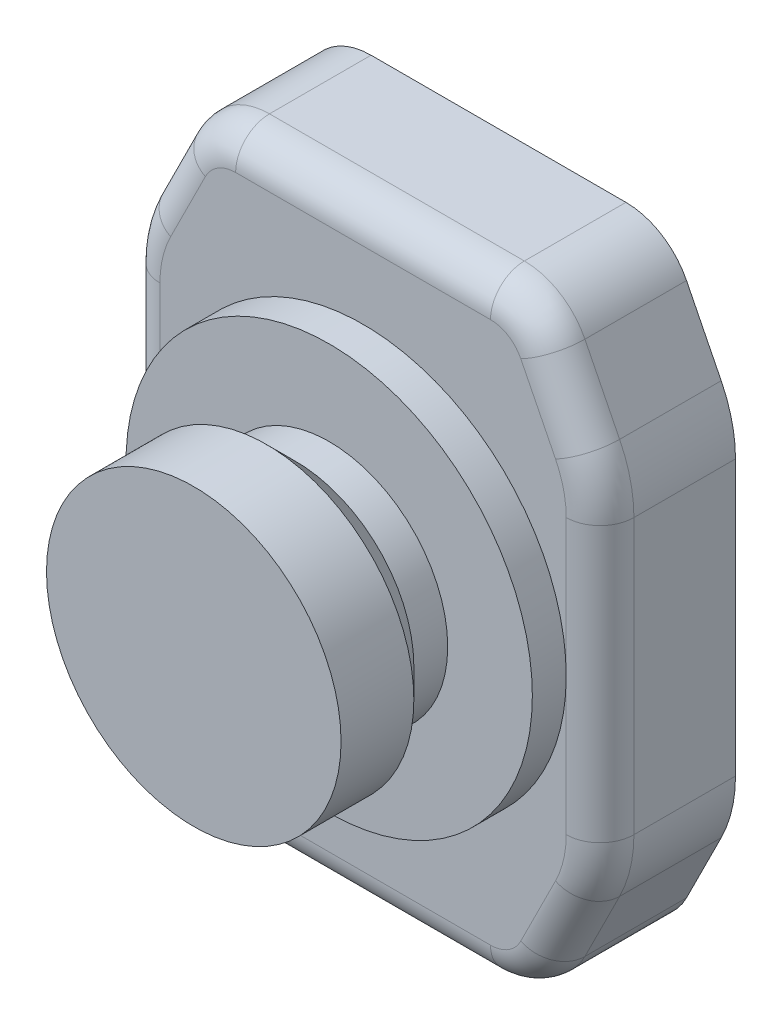
SolidWorks part; units mm, degrees
ref_plane "Front Plane" through (0, 0, 0) normal (0, 0, 1) x (1, 0, 0)
ref_plane "Top Plane" through (0, 0, 0) normal (0, 1, 0) x (1, 0, 0)
ref_plane "Right Plane" through (0, 0, 0) normal (1, 0, 0) x (0, 0, -1)
sketch "Sketch1" plane through (0, 0, 0) normal (0, 0, 1) x (1, 0, 0)
  line L0 (-32.8885, 29.2229) -> (-27.7639, 39.4721)
  line L1 (-18.8197, -45) -> (18.8197, -45)
  line L2 (-35, -20.2786) -> (-35, 20.2786)
  line L3 (-18.8197, 45) -> (18.8197, 45)
  line L4 (35, -20.2786) -> (35, 20.2786)
  line L5 (-35, -45) -> (35, 45) construction
  line L6 (-35, 45) -> (35, -45) construction
  line L7 (27.7639, 39.4721) -> (32.8885, 29.2229)
  line L8 (-32.8885, -29.2229) -> (-27.7639, -39.4721)
  line L9 (27.7639, -39.4721) -> (32.8885, -29.2229)
  arc A0 (-27.7639, -39.4721) -> (-18.8197, -45) centre (-18.8197, -35) ccw
  arc A1 (27.7639, -39.4721) -> (18.8197, -45) centre (18.8197, -35) cw
  arc A2 (27.7639, 39.4721) -> (18.8197, 45) centre (18.8197, 35) ccw
  arc A3 (-27.7639, 39.4721) -> (-18.8197, 45) centre (-18.8197, 35) cw
  arc A4 (32.8885, 29.2229) -> (35, 20.2786) centre (15, 20.2786) cw
  arc A5 (32.8885, -29.2229) -> (35, -20.2786) centre (15, -20.2786) ccw
  arc A6 (-32.8885, -29.2229) -> (-35, -20.2786) centre (-15, -20.2786) cw
  arc A7 (-32.8885, 29.2229) -> (-35, 20.2786) centre (-15, 20.2786) ccw
  point P0 (0, 0)
  point P16 (-25, -45)
  point P19 (25, -45)
  point P22 (25, 45)
  point P25 (-25, 45)
  point P28 (35, 25)
  point P31 (35, -25)
  point P34 (-35, -25)
  point P37 (-35, 25)
  dimension "D11" = 10
  dimension "D12" = 20
  dimension "D1" = 70
  dimension "D2" = 90
  dimension "D3" = 20
  dimension "D4" = 10
  dimension "D5" = 10
  dimension "D6" = 20
  dimension "D7" = 10
  dimension "D8" = 20
  dimension "D9" = 10
  dimension "D10" = 20
extrude "Boss-Extrude1" add sketch "Sketch1" along normal blind 20
fillet "Fillet1" radius 5 16 edges at (-30.3262, -34.3475, 20) (-34.465, -24.8737, 20) (-35, 0, 20) (-34.465, 24.8737, 20) (-30.3262, 34.3475, 20) (-24.077, 43.5065, 20) (0, 45, 20) (24.077, 43.5065, 20) (30.3262, 34.3475, 20) (34.465, 24.8737, 20) (35, 0, 20) (34.465, -24.8737, 20) (30.3262, -34.3475, 20) (24.077, -43.5065, 20) (0, -45, 20) (-24.077, -43.5065, 20)
sketch "Sketch2" plane through (0, 0, 20) normal (0, 0, 1) x (1, 0, 0)
  circle A0 centre (0, 0) radius 30
  dimension "D1" = 60
extrude "Boss-Extrude2" add sketch "Sketch2" along normal blind 5
sketch "Sketch3" plane through (0, 0, 25) normal (0, 0, 1) x (1, 0, 0)
  circle A0 centre (0, 0) radius 17.5
  dimension "D1" = 35
extrude "Boss-Extrude3" add sketch "Sketch3" along normal blind 10
sketch "Sketch4" plane through (0, 0, 35) normal (0, 0, 1) x (1, 0, 0)
  circle A0 centre (0, 0) radius 21.75
  dimension "D1" = 43.5
extrude "Boss-Extrude4" add sketch "Sketch4" along normal blind 10
chamfer "Chamfer1" distance 5 angle 45 1 edges at (17.5, 0, 35)
